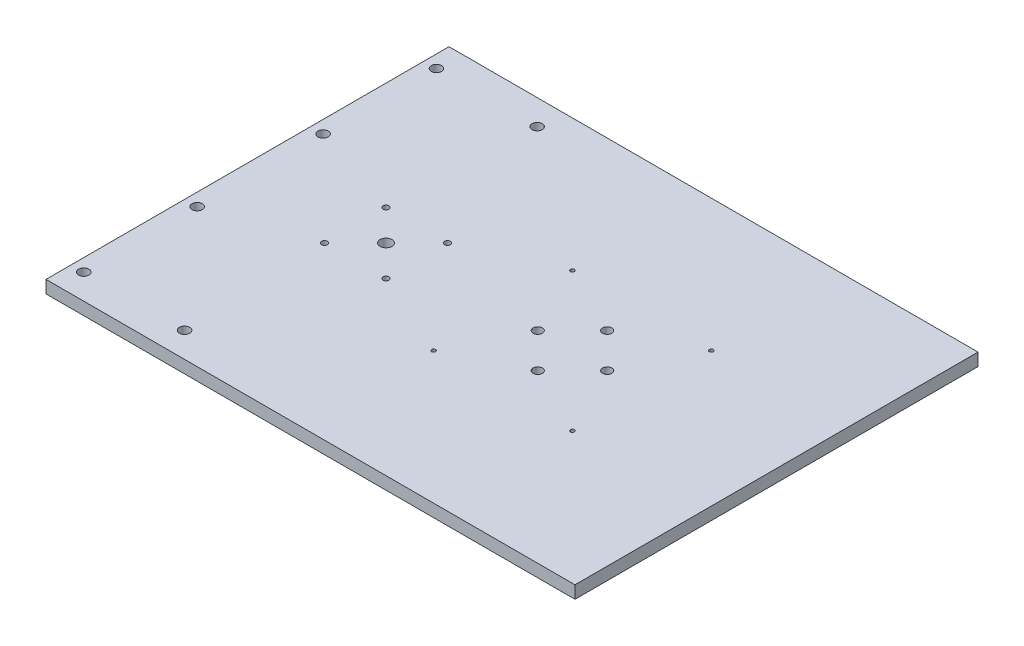
SolidWorks part; units mm, degrees
ref_plane "Front Plane" through (0, 0, 0) normal (0, 0, 1) x (1, 0, 0)
ref_plane "Top Plane" through (0, 0, 0) normal (0, 1, 0) x (1, 0, 0)
ref_plane "Right Plane" through (0, 0, 0) normal (1, 0, 0) x (0, 0, -1)
sketch "Sketch1" plane through (0, 0, 0) normal (0, 1, 0) x (1, 0, 0)
  line L1 (-133.35, -101.6) -> (133.35, -101.6)
  line L2 (-133.35, -101.6) -> (-133.35, 101.6)
  line L3 (-133.35, 101.6) -> (133.35, 101.6)
  line L4 (133.35, -101.6) -> (133.35, 101.6)
  line L5 (-133.35, -101.6) -> (133.35, 101.6) construction
  line L6 (-133.35, 101.6) -> (133.35, -101.6) construction
  point P0 (0, 0)
  dimension "D1" = 203.2
  dimension "D2" = 266.7
extrude "Boss-Extrude1" add sketch "Sketch1" along normal blind 6.35
sketch "Sketch2" plane through (0, 0, 0) normal (0, 1, 0) x (1, 0, 0)
  line L0 (-193.2668, 0) -> (192.9727, 0) construction
sketch "Sketch3" plane through (0, 6.35, 0) normal (0, 1, 0) x (1, 0, 0)
  circle A1 centre (-127, -31.75) radius 2.6
  circle A2 centre (-127, -31.75) radius 2.6
  circle A3 centre (-76.2, -88.9) radius 2.6
  circle A4 centre (-76.2, -88.9) radius 2.6
  circle A5 centre (-127, -88.9) radius 2.6
  circle A6 centre (-127, -88.9) radius 2.6
  dimension "D1" = 0
  dimension "D2" = 0
  dimension "D3" = 0
sketch "Sketch5" plane through (0, 6.35, 0) normal (0, 1, 0) x (1, 0, 0)
  circle A0 centre (-48.024, 15.5) radius 1.5 construction
  circle A1 centre (-48.024, -15.5) radius 1.5 construction
  circle A2 centre (-79.024, 15.5) radius 1.5 construction
  circle A3 centre (-79.024, -15.5) radius 1.5 construction
  circle A4 centre (-63.524, 0) radius 2.5 construction
  circle A5 centre (-48.024, 15.5) radius 1.5
  circle A6 centre (-48.024, -15.5) radius 1.5
  circle A7 centre (-79.024, 15.5) radius 1.5
  circle A8 centre (-79.024, -15.5) radius 1.5
  circle A9 centre (-63.524, 0) radius 2.5 construction
  circle A10 centre (-63.524, 0) radius 3.008
  dimension "D1" = 6.016
sketch "Sketch7" plane through (0, 6.35, 0) normal (0, 1, 0) x (1, 0, 0)
  circle A0 centre (65.4818, -35.0018) radius 1 construction
  circle A1 centre (-4.5218, -35.0018) radius 1 construction
  circle A2 centre (65.4818, -35.0018) radius 1
  circle A3 centre (-4.5218, -35.0018) radius 1
  circle A4 centre (-4.5218, 35.0018) radius 1 construction
  circle A5 centre (65.4818, 35.0018) radius 1 construction
  circle A6 centre (-4.5218, 35.0018) radius 1
  circle A7 centre (65.4818, 35.0018) radius 1
extrude "Cut-Extrude1" cut sketch "Sketch3" against normal through all
mirror "Mirror1" about plane through (0, 0, 0) normal (0, 0, 1) of "Cut-Extrude1"
extrude "Cut-Extrude2" cut sketch "Sketch5" against normal through all
extrude "Cut-Extrude3" cut sketch "Sketch7" against normal through all
sketch "Sketch8" plane through (0, 6.35, 0) normal (0, 1, 0) x (1, 0, 0)
  arc A0 (30.48, -19.85) -> (30.48, -15.15) centre (30.48, -17.5) ccw construction
  arc A1 (30.48, -19.85) -> (30.48, -15.15) centre (30.48, -17.5) ccw
  arc A2 (30.48, -15.15) -> (30.48, -19.85) centre (30.48, -17.5) ccw construction
  arc A3 (30.48, -15.15) -> (30.48, -19.85) centre (30.48, -17.5) ccw
  circle A4 centre (12.98, 0) radius 2.35 construction
  circle A5 centre (12.98, 0) radius 2.35
  arc A6 (30.48, 15.15) -> (30.48, 19.85) centre (30.48, 17.5) ccw construction
  arc A7 (30.48, 15.15) -> (30.48, 19.85) centre (30.48, 17.5) ccw
  arc A8 (30.48, 19.85) -> (30.48, 15.15) centre (30.48, 17.5) ccw construction
  arc A9 (30.48, 19.85) -> (30.48, 15.15) centre (30.48, 17.5) ccw
  circle A10 centre (47.98, 0) radius 2.35 construction
  circle A11 centre (47.98, 0) radius 2.35
extrude "Cut-Extrude4" cut sketch "Sketch8" against normal through all
equation "\"tightTol\"= 0.005in"
equation "\"normTol\"= 0.01in"
equation "\"looseTol\"= 0.02in"
equation "\"D1@Sketch5\"=5mm+2*\"looseTol\""
